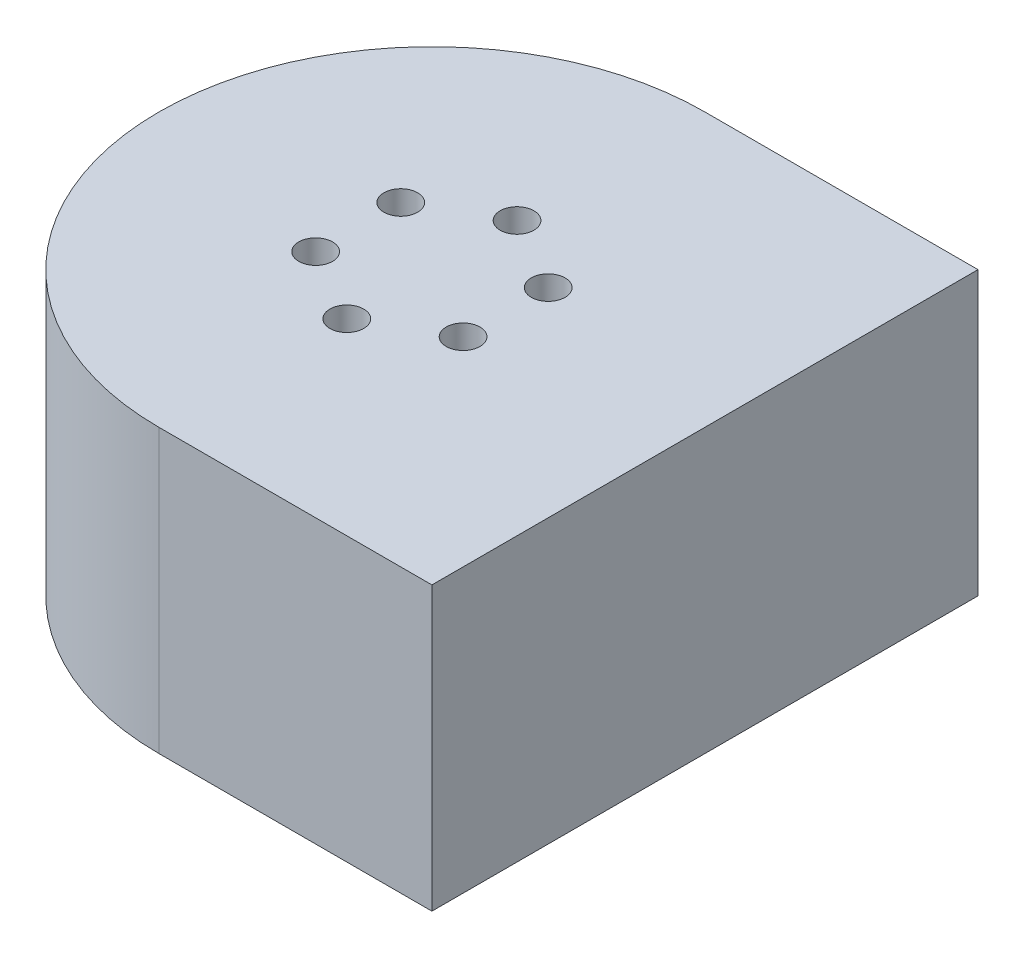
SolidWorks part; units mm, degrees
ref_plane "Front Plane" through (0, 0, 0) normal (0, 0, 1) x (1, 0, 0)
ref_plane "Top Plane" through (0, 0, 0) normal (0, 1, 0) x (1, 0, 0)
ref_plane "Right Plane" through (0, 0, 0) normal (1, 0, 0) x (0, 0, -1)
sketch "Sketch1" plane through (0, 0, 0) normal (0, 1, 0) x (1, 0, 0)
  line L0 (0, 44.45) -> (44.45, 44.45)
  line L1 (44.45, 44.45) -> (44.45, -44.45)
  line L2 (44.45, -44.45) -> (0, -44.45)
  arc A0 (0, 44.45) -> (0, -44.45) centre (0, 0) ccw
extrude "Boss-Extrude1" add sketch "Sketch1" along normal blind 46
sketch "Sketch2" plane through (0, 0, 0) normal (0, -1, 0) x (-1, 0, 0)
  line L1 (0, -13.8564) -> (12, -6.9282)
  line L2 (12, -6.9282) -> (12, 6.9282)
  line L3 (12, 6.9282) -> (0, 13.8564)
  line L4 (0, 13.8564) -> (-12, 6.9282)
  line L5 (-12, 6.9282) -> (-12, -6.9282)
  line L6 (-12, -6.9282) -> (0, -13.8564)
  circle A0 centre (0, 0) radius 12 construction
  circle A1 centre (0, -13.8564) radius 2.75
  circle A2 centre (12, -6.9282) radius 2.75
  circle A3 centre (12, 6.9282) radius 2.75
  circle A4 centre (0, 13.8564) radius 2.75
  circle A5 centre (-12, 6.9282) radius 2.75
  circle A6 centre (-12, -6.9282) radius 2.75
extrude "Cut-Extrude2" cut sketch "Sketch2" against normal blind 76 contours L6 A1 L1 | L5 A6 L6 | L4 A5 L5 | L3 A4 L4 | L2 A3 L3 | L1 A2 L2 | L2 A2 L1 | L1 A1 L6 | L6 A6 L5 | L5 A5 L4 | L4 A4 L3 | L3 A3 L2 region at (0, 0, 12.3403) region at (0, 0, 14.6145) region at (-10.687, 0, 6.1701) region at (-12.6565, 0, 7.3072) region at (12.6565, 0, 7.3072) region at (10.687, 0, 6.1701) region at (-10.687, 0, -6.1701) region at (-12.6565, 0, -7.3072) region at (12.6565, 0, -7.3072) region at (10.687, 0, -6.1701) region at (0, 0, -12.3403) region at (0, 0, -14.6145)
